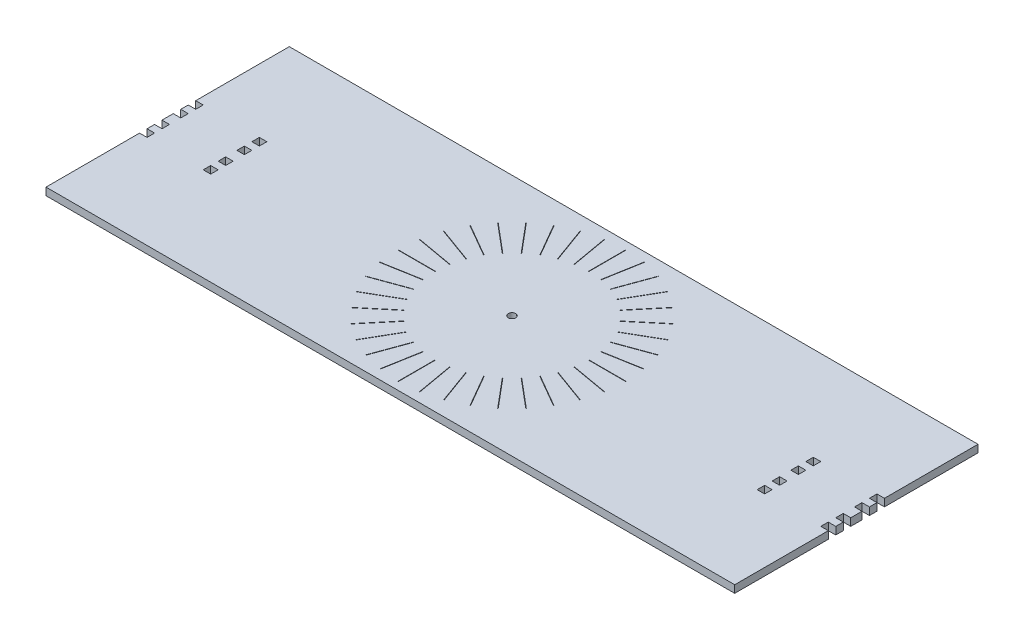
SolidWorks part; units mm, degrees
ref_plane "Front Plane" through (0, 0, 0) normal (0, 0, 1) x (1, 0, 0)
ref_plane "Top Plane" through (0, 0, 0) normal (0, 1, 0) x (1, 0, 0)
ref_plane "Right Plane" through (0, 0, 0) normal (1, 0, 0) x (0, 0, -1)
sketch "Sketch1" plane through (0, 0, 0) normal (0, 1, 0) x (1, 0, 0)
  line L0 (5.0985, 87.9487) -> (5.0985, -77.1513) construction
  line L1 (-228.5815, 87.9487) -> (238.7785, 87.9487)
  line L2 (-228.5815, 87.9487) -> (-228.5815, -77.1513)
  line L3 (-228.5815, -77.1513) -> (238.7785, -77.1513)
  line L4 (238.7785, 87.9487) -> (238.7785, -77.1513)
  line L5 (-228.5815, 5.3987) -> (238.7785, 5.3987) construction
  line L6 (-228.5815, -13.6513) -> (238.7785, -13.6513) construction
  line L7 (-228.5815, 24.4487) -> (238.7785, 24.4487) construction
  circle A0 centre (5.0985, 5.3987) radius 2.54
  dimension "D3" = 5.08
  dimension "D1" = 467.36
  dimension "D2" = 165.1
  dimension "D4" = 19.05
  dimension "D5" = 19.05
extrude "Boss-Extrude1" add sketch "Sketch1" along normal blind 5.08
sketch "Sketch2" plane through (0, 5.08, 0) normal (0, 1, 0) x (1, 0, 0)
  line L0 (5.0985, 87.9487) -> (5.0985, -77.1513) construction
  line L1 (238.7785, 87.9487) -> (-228.5815, 87.9487) construction
  line L2 (-228.5815, -77.1513) -> (238.7785, -77.1513) construction
  line L3 (-228.5815, 5.3987) -> (238.7785, 5.3987) construction
  line L4 (-228.5815, 87.9487) -> (-228.5815, -77.1513) construction
  line L5 (238.7785, -77.1513) -> (238.7785, 87.9487) construction
  line L6 (-228.5815, -13.6513) -> (238.7785, -13.6513) construction
  line L7 (-228.5815, 24.4487) -> (238.7785, 24.4487) construction
  line L8 (-185.4015, 87.9487) -> (-185.4015, -77.1513) construction
  line L9 (-228.5815, 24.4487) -> (-223.5015, 24.4487)
  line L10 (-228.5815, 24.4487) -> (-228.5815, 19.3687)
  line L11 (-228.5815, 19.3687) -> (-223.5015, 19.3687)
  line L12 (-223.5015, 24.4487) -> (-223.5015, 19.3687)
  line L13 (-228.5815, -13.6513) -> (-223.5015, -13.6513)
  line L14 (-228.5815, -13.6513) -> (-228.5815, -8.5713)
  line L15 (-228.5815, -8.5713) -> (-223.5015, -8.5713)
  line L16 (-223.5015, -13.6513) -> (-223.5015, -8.5713)
  line L17 (-228.5815, 14.2887) -> (-223.5015, 14.2887)
  line L18 (-228.5815, 14.2887) -> (-228.5815, 9.2087)
  line L19 (-228.5815, 9.2087) -> (-223.5015, 9.2087)
  line L20 (-223.5015, 14.2887) -> (-223.5015, 9.2087)
  line L21 (-228.5815, -3.4913) -> (-223.5015, -3.4913)
  line L22 (-228.5815, -3.4913) -> (-228.5815, 1.5887)
  line L23 (-228.5815, 1.5887) -> (-223.5015, 1.5887)
  line L24 (-223.5015, -3.4913) -> (-223.5015, 1.5887)
  line L25 (-185.4015, 24.4487) -> (-185.4015, 19.3687)
  line L26 (-185.4015, 1.5887) -> (-180.3215, 1.5887)
  line L27 (-185.4015, -13.6513) -> (-180.3215, -13.6513)
  line L28 (-185.4015, -3.4913) -> (-185.4015, 1.5887)
  line L29 (-185.4015, -8.5713) -> (-180.3215, -8.5713)
  line L30 (-185.4015, 19.3687) -> (-180.3215, 19.3687)
  line L31 (-180.3215, 24.4487) -> (-180.3215, 19.3687)
  line L32 (-185.4015, 9.2087) -> (-180.3215, 9.2087)
  line L33 (-185.4015, 14.2887) -> (-180.3215, 14.2887)
  line L34 (-185.4015, 24.4487) -> (-180.3215, 24.4487)
  line L35 (-185.4015, -13.6513) -> (-185.4015, -8.5713)
  line L36 (-185.4015, -3.4913) -> (-180.3215, -3.4913)
  line L37 (-180.3215, -3.4913) -> (-180.3215, 1.5887)
  line L38 (-185.4015, 14.2887) -> (-185.4015, 9.2087)
  line L39 (-180.3215, -13.6513) -> (-180.3215, -8.5713)
  line L40 (-180.3215, 14.2887) -> (-180.3215, 9.2087)
  line L41 (190.5185, 14.2887) -> (190.5185, 9.2087)
  line L42 (190.5185, -13.6513) -> (190.5185, -8.5713)
  line L43 (195.5985, 14.2887) -> (195.5985, 9.2087)
  line L44 (190.5185, -3.4913) -> (190.5185, 1.5887)
  line L45 (195.5985, -3.4913) -> (190.5185, -3.4913)
  line L46 (195.5985, -13.6513) -> (195.5985, -8.5713)
  line L47 (195.5985, 24.4487) -> (190.5185, 24.4487)
  line L48 (195.5985, 14.2887) -> (190.5185, 14.2887)
  line L49 (195.5985, 9.2087) -> (190.5185, 9.2087)
  line L50 (190.5185, 24.4487) -> (190.5185, 19.3687)
  line L51 (195.5985, 19.3687) -> (190.5185, 19.3687)
  line L52 (195.5985, -8.5713) -> (190.5185, -8.5713)
  line L53 (195.5985, -3.4913) -> (195.5985, 1.5887)
  line L54 (195.5985, -13.6513) -> (190.5185, -13.6513)
  line L55 (195.5985, 1.5887) -> (190.5185, 1.5887)
  line L56 (195.5985, 24.4487) -> (195.5985, 19.3687)
  line L57 (233.6985, -3.4913) -> (233.6985, 1.5887)
  line L58 (238.7785, 1.5887) -> (233.6985, 1.5887)
  line L59 (238.7785, -3.4913) -> (238.7785, 1.5887)
  line L60 (238.7785, -3.4913) -> (233.6985, -3.4913)
  line L61 (233.6985, 14.2887) -> (233.6985, 9.2087)
  line L62 (238.7785, 9.2087) -> (233.6985, 9.2087)
  line L63 (238.7785, 14.2887) -> (238.7785, 9.2087)
  line L64 (238.7785, 14.2887) -> (233.6985, 14.2887)
  line L65 (233.6985, -13.6513) -> (233.6985, -8.5713)
  line L66 (238.7785, -8.5713) -> (233.6985, -8.5713)
  line L67 (238.7785, -13.6513) -> (238.7785, -8.5713)
  line L68 (238.7785, -13.6513) -> (233.6985, -13.6513)
  line L69 (233.6985, 24.4487) -> (233.6985, 19.3687)
  line L70 (238.7785, 19.3687) -> (233.6985, 19.3687)
  line L71 (238.7785, 24.4487) -> (238.7785, 19.3687)
  line L72 (238.7785, 24.4487) -> (233.6985, 24.4487)
  dimension "D3" = 5.08
  dimension "D4" = 5.08
  dimension "D5" = 5.08
  dimension "D6" = 5.08
  dimension "D7" = 5.08
  dimension "D8" = 5.08
  dimension "D9" = 5.08
  dimension "D10" = 5.08
  dimension "D11" = 5.08
  dimension "D12" = 5.08
  dimension "D13" = 43.18
  dimension "D14" = 5.08
  dimension "D15" = 5.08
  dimension "D16" = 5.08
  dimension "D17" = 5.08
  dimension "D18" = 5.08
  dimension "D19" = 5.08
  dimension "D1" = 19.05
  dimension "D2" = 19.05
extrude "Cut-Extrude1" cut sketch "Sketch2" against normal blind 5.08
sketch "Sketch3" plane through (0, 5.08, 0) normal (0, 1, 0) x (1, 0, 0)
  line L0 (5.0985, 87.9487) -> (5.0985, -77.1513) construction
  line L1 (238.7785, 87.9487) -> (-228.5815, 87.9487) construction
  line L2 (-228.5815, -77.1513) -> (238.7785, -77.1513) construction
  line L3 (-228.5815, 5.3987) -> (238.7785, 5.3987) construction
  line L4 (-228.5815, 9.2087) -> (-228.5815, 1.5887) construction
  line L5 (238.7785, 1.5887) -> (238.7785, 9.2087) construction
  line L6 (18.4259, 81.7138) -> (18.6761, 81.6697)
  line L7 (4.9715, 82.8687) -> (5.2255, 82.8687)
  line L8 (4.9715, 82.8687) -> (4.9715, 57.4687)
  line L9 (4.9715, 57.4687) -> (5.2255, 57.4687)
  line L10 (5.2255, 82.8687) -> (5.2255, 57.4687)
  line L11 (18.4259, 81.7138) -> (14.0153, 56.6996)
  line L12 (14.0153, 56.6996) -> (14.2654, 56.6555)
  line L13 (18.6761, 81.6697) -> (14.2654, 56.6555)
  line L14 (31.4754, 78.2401) -> (31.7141, 78.1532)
  line L15 (31.4754, 78.2401) -> (22.7881, 54.3719)
  line L16 (22.7881, 54.3719) -> (23.0268, 54.285)
  line L17 (31.7141, 78.1532) -> (23.0268, 54.285)
  line L18 (43.7235, 72.5531) -> (43.9435, 72.4261)
  line L19 (43.7235, 72.5531) -> (31.0235, 50.5561)
  line L20 (31.0235, 50.5561) -> (31.2435, 50.4291)
  line L21 (43.9435, 72.4261) -> (31.2435, 50.4291)
  line L22 (54.7979, 64.8258) -> (54.9925, 64.6625)
  line L23 (54.7979, 64.8258) -> (38.4711, 45.3682)
  line L24 (38.4711, 45.3682) -> (38.6657, 45.205)
  line L25 (54.9925, 64.6625) -> (38.6657, 45.205)
  line L26 (64.3623, 55.2927) -> (64.5256, 55.0981)
  line L27 (64.3623, 55.2927) -> (44.9048, 38.9659)
  line L28 (44.9048, 38.9659) -> (45.068, 38.7713)
  line L29 (64.5256, 55.0981) -> (45.068, 38.7713)
  line L30 (72.126, 44.2436) -> (72.253, 44.0237)
  line L31 (72.126, 44.2436) -> (50.1289, 31.5436)
  line L32 (50.1289, 31.5436) -> (50.2559, 31.3237)
  line L33 (72.253, 44.0237) -> (50.2559, 31.3237)
  line L34 (77.853, 32.0143) -> (77.9399, 31.7756)
  line L35 (77.853, 32.0143) -> (53.9848, 23.327)
  line L36 (53.9848, 23.327) -> (54.0717, 23.0883)
  line L37 (77.9399, 31.7756) -> (54.0717, 23.0883)
  line L38 (81.3695, 18.9762) -> (81.4136, 18.7261)
  line L39 (81.3695, 18.9762) -> (56.3554, 14.5656)
  line L40 (56.3554, 14.5656) -> (56.3995, 14.3154)
  line L41 (81.4136, 18.7261) -> (56.3995, 14.3154)
  line L42 (82.5685, 5.5257) -> (82.5685, 5.2717)
  line L43 (82.5685, 5.5257) -> (57.1685, 5.5257)
  line L44 (57.1685, 5.5257) -> (57.1685, 5.2717)
  line L45 (82.5685, 5.2717) -> (57.1685, 5.2717)
  line L46 (81.4136, -7.9288) -> (81.3695, -8.1789)
  line L47 (81.4136, -7.9288) -> (56.3995, -3.5181)
  line L48 (56.3995, -3.5181) -> (56.3554, -3.7683)
  line L49 (81.3695, -8.1789) -> (56.3554, -3.7683)
  line L50 (77.9399, -20.9783) -> (77.853, -21.217)
  line L51 (77.9399, -20.9783) -> (54.0717, -12.291)
  line L52 (54.0717, -12.291) -> (53.9848, -12.5297)
  line L53 (77.853, -21.217) -> (53.9848, -12.5297)
  line L54 (72.253, -33.2264) -> (72.126, -33.4463)
  line L55 (72.253, -33.2264) -> (50.2559, -20.5264)
  line L56 (50.2559, -20.5264) -> (50.1289, -20.7463)
  line L57 (72.126, -33.4463) -> (50.1289, -20.7463)
  line L58 (64.5256, -44.3008) -> (64.3623, -44.4954)
  line L59 (64.5256, -44.3008) -> (45.068, -27.974)
  line L60 (45.068, -27.974) -> (44.9048, -28.1686)
  line L61 (64.3623, -44.4954) -> (44.9048, -28.1686)
  line L62 (54.9925, -53.8652) -> (54.7979, -54.0284)
  line L63 (54.9925, -53.8652) -> (38.6657, -34.4076)
  line L64 (38.6657, -34.4076) -> (38.4711, -34.5709)
  line L65 (54.7979, -54.0284) -> (38.4711, -34.5709)
  line L66 (43.9435, -61.6288) -> (43.7235, -61.7558)
  line L67 (43.9435, -61.6288) -> (31.2435, -39.6318)
  line L68 (31.2435, -39.6318) -> (31.0235, -39.7588)
  line L69 (43.7235, -61.7558) -> (31.0235, -39.7588)
  line L70 (31.7141, -67.3559) -> (31.4754, -67.4428)
  line L71 (31.7141, -67.3559) -> (23.0268, -43.4877)
  line L72 (23.0268, -43.4877) -> (22.7881, -43.5746)
  line L73 (31.4754, -67.4428) -> (22.7881, -43.5746)
  line L74 (18.6761, -70.8723) -> (18.4259, -70.9165)
  line L75 (18.6761, -70.8723) -> (14.2654, -45.8582)
  line L76 (14.2654, -45.8582) -> (14.0153, -45.9023)
  line L77 (18.4259, -70.9165) -> (14.0153, -45.9023)
  line L78 (5.2255, -72.0713) -> (4.9715, -72.0713)
  line L79 (5.2255, -72.0713) -> (5.2255, -46.6713)
  line L80 (5.2255, -46.6713) -> (4.9715, -46.6713)
  line L81 (4.9715, -72.0713) -> (4.9715, -46.6713)
  line L82 (-8.229, -70.9165) -> (-8.4791, -70.8723)
  line L83 (-8.229, -70.9165) -> (-3.8183, -45.9023)
  line L84 (-3.8183, -45.9023) -> (-4.0685, -45.8582)
  line L85 (-8.4791, -70.8723) -> (-4.0685, -45.8582)
  line L86 (-21.2785, -67.4428) -> (-21.5172, -67.3559)
  line L87 (-21.2785, -67.4428) -> (-12.5912, -43.5746)
  line L88 (-12.5912, -43.5746) -> (-12.8299, -43.4877)
  line L89 (-21.5172, -67.3559) -> (-12.8299, -43.4877)
  line L90 (-33.5265, -61.7558) -> (-33.7465, -61.6288)
  line L91 (-33.5265, -61.7558) -> (-20.8265, -39.7588)
  line L92 (-20.8265, -39.7588) -> (-21.0465, -39.6318)
  line L93 (-33.7465, -61.6288) -> (-21.0465, -39.6318)
  line L94 (-44.601, -54.0284) -> (-44.7956, -53.8652)
  line L95 (-44.601, -54.0284) -> (-28.2742, -34.5709)
  line L96 (-28.2742, -34.5709) -> (-28.4688, -34.4076)
  line L97 (-44.7956, -53.8652) -> (-28.4688, -34.4076)
  line L98 (-54.1654, -44.4954) -> (-54.3286, -44.3008)
  line L99 (-54.1654, -44.4954) -> (-34.7078, -28.1686)
  line L100 (-34.7078, -28.1686) -> (-34.8711, -27.974)
  line L101 (-54.3286, -44.3008) -> (-34.8711, -27.974)
  line L102 (-61.929, -33.4463) -> (-62.056, -33.2264)
  line L103 (-61.929, -33.4463) -> (-39.932, -20.7463)
  line L104 (-39.932, -20.7463) -> (-40.059, -20.5264)
  line L105 (-62.056, -33.2264) -> (-40.059, -20.5264)
  line L106 (-67.6561, -21.217) -> (-67.743, -20.9783)
  line L107 (-67.6561, -21.217) -> (-43.7879, -12.5297)
  line L108 (-43.7879, -12.5297) -> (-43.8748, -12.291)
  line L109 (-67.743, -20.9783) -> (-43.8748, -12.291)
  line L110 (-71.1725, -8.1789) -> (-71.2166, -7.9288)
  line L111 (-71.1725, -8.1789) -> (-46.1584, -3.7683)
  line L112 (-46.1584, -3.7683) -> (-46.2025, -3.5181)
  line L113 (-71.2166, -7.9288) -> (-46.2025, -3.5181)
  line L114 (-72.3715, 5.2717) -> (-72.3715, 5.5257)
  line L115 (-72.3715, 5.2717) -> (-46.9715, 5.2717)
  line L116 (-46.9715, 5.2717) -> (-46.9715, 5.5257)
  line L117 (-72.3715, 5.5257) -> (-46.9715, 5.5257)
  line L118 (-71.2166, 18.7261) -> (-71.1725, 18.9762)
  line L119 (-71.2166, 18.7261) -> (-46.2025, 14.3154)
  line L120 (-46.2025, 14.3154) -> (-46.1584, 14.5656)
  line L121 (-71.1725, 18.9762) -> (-46.1584, 14.5656)
  line L122 (-67.743, 31.7756) -> (-67.6561, 32.0143)
  line L123 (-67.743, 31.7756) -> (-43.8748, 23.0883)
  line L124 (-43.8748, 23.0883) -> (-43.7879, 23.327)
  line L125 (-67.6561, 32.0143) -> (-43.7879, 23.327)
  line L126 (-62.056, 44.0237) -> (-61.929, 44.2436)
  line L127 (-62.056, 44.0237) -> (-40.059, 31.3237)
  line L128 (-40.059, 31.3237) -> (-39.932, 31.5436)
  line L129 (-61.929, 44.2436) -> (-39.932, 31.5436)
  line L130 (-54.3286, 55.0981) -> (-54.1654, 55.2927)
  line L131 (-54.3286, 55.0981) -> (-34.8711, 38.7713)
  line L132 (-34.8711, 38.7713) -> (-34.7078, 38.9659)
  line L133 (-54.1654, 55.2927) -> (-34.7078, 38.9659)
  line L134 (-44.7956, 64.6625) -> (-44.601, 64.8258)
  line L135 (-44.7956, 64.6625) -> (-28.4688, 45.205)
  line L136 (-28.4688, 45.205) -> (-28.2742, 45.3682)
  line L137 (-44.601, 64.8258) -> (-28.2742, 45.3682)
  line L138 (-33.7465, 72.4261) -> (-33.5265, 72.5531)
  line L139 (-33.7465, 72.4261) -> (-21.0465, 50.4291)
  line L140 (-21.0465, 50.4291) -> (-20.8265, 50.5561)
  line L141 (-33.5265, 72.5531) -> (-20.8265, 50.5561)
  line L142 (-21.5172, 78.1532) -> (-21.2785, 78.2401)
  line L143 (-21.5172, 78.1532) -> (-12.8299, 54.285)
  line L144 (-12.8299, 54.285) -> (-12.5912, 54.3719)
  line L145 (-21.2785, 78.2401) -> (-12.5912, 54.3719)
  line L146 (-8.4791, 81.6697) -> (-8.229, 81.7138)
  line L147 (-8.4791, 81.6697) -> (-4.0685, 56.6555)
  line L148 (-4.0685, 56.6555) -> (-3.8183, 56.6996)
  line L149 (-8.229, 81.7138) -> (-3.8183, 56.6996)
  point P16 (5.0985, 5.3987)
  point P160 (5.0985, 5.3987)
  dimension "D1" = 0.127
  dimension "D2" = 0.254
  dimension "D3" = 5.08
  dimension "D4" = 25.4
  dimension "D5" = 36
extrude "Cut-Extrude2" cut sketch "Sketch3" against normal blind 5.08
